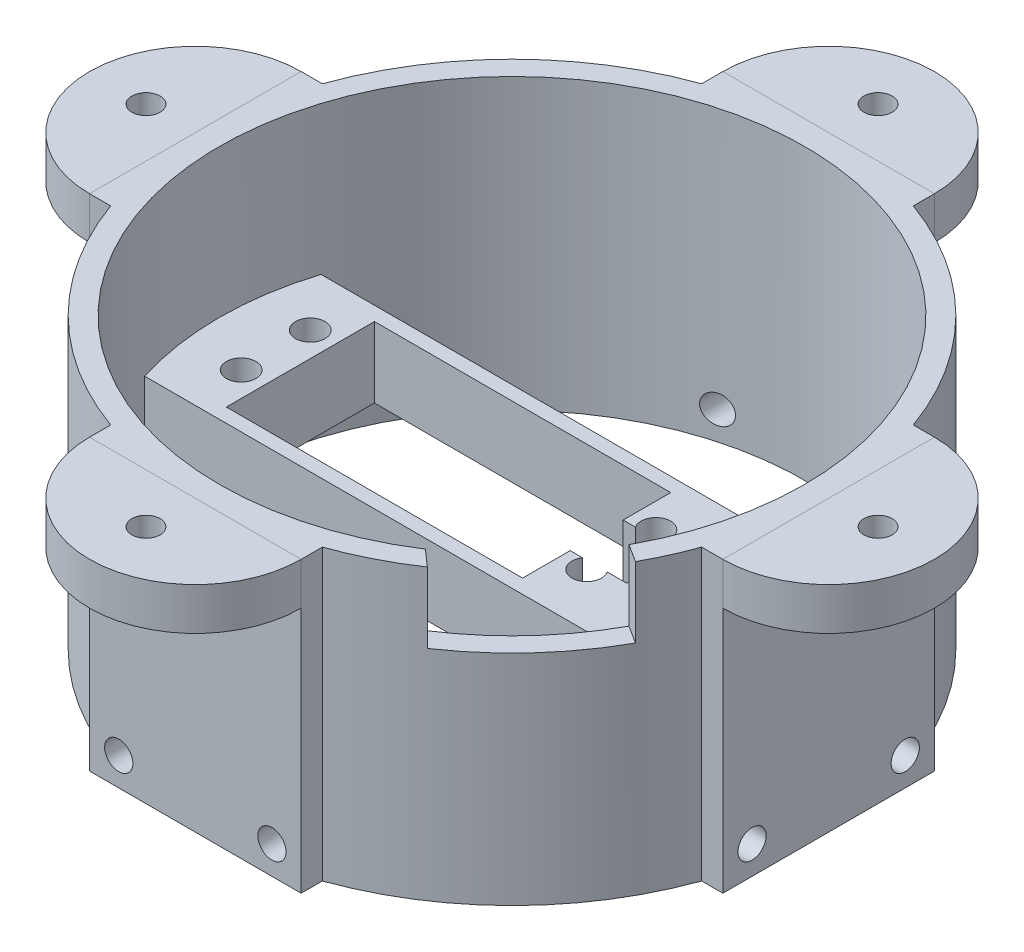
SolidWorks part; units mm, degrees
ref_plane "Front Plane" through (0, 0, 0) normal (0, 0, 1) x (1, 0, 0)
ref_plane "Top Plane" through (0, 0, 0) normal (0, 1, 0) x (1, 0, 0)
ref_plane "Right Plane" through (0, 0, 0) normal (1, 0, 0) x (0, 0, -1)
sketch "Sketch1" plane through (0, 0, 0) normal (0, 1, 0) x (1, 0, 0)
  circle A0 centre (0, 0) radius 44.5
  circle A1 centre (0, 0) radius 41.5
  dimension "D1" = 3
  dimension "D2" = 83
extrude "Boss-Extrude1" add sketch "Sketch1" along normal blind 41
sketch "Sketch2" plane through (0, 0, 0) normal (0, 1, 0) x (1, 0, 0)
  line L0 (-39.5727, 12.5) -> (39.5727, 12.5)
  line L1 (-39.5727, -12.5) -> (39.5727, -12.5)
  line L2 (-9, 10.5) -> (-9, -15.318) construction
  line L3 (-30, 10.5) -> (12, 10.5)
  line L4 (-30, 10.5) -> (-30, -10.5)
  line L5 (-30, -10.5) -> (12, -10.5)
  line L6 (12, 10.5) -> (12, -10.5)
  circle A0 centre (0, 0) radius 41.5 construction
  arc A1 (-39.5727, 12.5) -> (-39.5727, -12.5) centre (-3.1584, 0) ccw
  arc A2 (39.5727, 12.5) -> (39.5727, -12.5) centre (3.1584, 0) cw
  circle A3 centre (15.5, 4.9) radius 2.1
  circle A4 centre (15.5, -4.9) radius 2.1
  circle A7 centre (-33.5, 4.9) radius 2.1
  circle A8 centre (-33.5, -4.9) radius 2.1
  point P6 (0, 0)
  dimension "D5" = 4.2
  dimension "D6" = 4.9
  dimension "D7" = 4.9
  dimension "D11" = 0
  dimension "D1" = 12.5
  dimension "D2" = 12.5
  dimension "D3" = 21
  dimension "D4" = 42
  dimension "D8" = 10.5
  dimension "D9" = 12
  dimension "D10" = 3.5
extrude "Boss-Extrude2" add sketch "Sketch2" along normal blind 20
sketch "Sketch3" plane through (0, 0, 0) normal (0, 1, 0) x (1, 0, 0)
  line L0 (0, 0) -> (0, 56.6556) construction
  line L1 (0, 44.8957) -> (-15, 44.8957)
  line L2 (-15, 44.8957) -> (-15, 41.8957)
  line L3 (0, 44.8957) -> (15, 44.8957)
  line L4 (15, 44.8957) -> (15, 41.8957)
  circle A0 centre (0, 0) radius 44.5 construction
  arc A1 (-15, 41.8957) -> (15, 41.8957) centre (0, 0) cw
  dimension "D1" = 15
  dimension "D2" = 15
  dimension "D3" = 3
extrude "Boss-Extrude3" add sketch "Sketch3" along normal blind 41
pattern_circular "CirPattern1" count 4 over 360 about axis through (0, 41, 0) along (0, -1, 0) of "Boss-Extrude3"
sketch "Sketch4" plane through (-44.8957, 0, 0) normal (-1, 0, 0) x (0, 0, 1)
  line L1 (0, 37.0728) -> (0, -4.8522) construction
  line L2 (-15, 0) -> (15, 0) construction
  line L3 (15, 41) -> (15, 0) construction
  circle A0 centre (10.8598, 4) radius 2
  circle A2 centre (-10.8598, 4) radius 2
  dimension "D1" = 4
  dimension "D2" = 4
  dimension "D3" = 4.1402
extrude "Cut-Extrude1" cut sketch "Sketch4" against normal blind 7
sketch "Sketch5" plane through (0, 0, 0) normal (0, 1, 0) x (1, 0, 0)
  line L0 (-39.5727, 12.5) -> (39.5727, 12.5)
  line L1 (-39.5727, -12.5) -> (39.5727, -12.5)
  arc A0 (-39.5727, 12.5) -> (-39.5727, -12.5) centre (0, 0) ccw
  arc A1 (39.5727, -12.5) -> (39.5727, 12.5) centre (0, 0) ccw
extrude "Cut-Extrude2" cut sketch "Sketch5" along normal blind 10
pattern_circular "CirPattern2" count 4 over 360 about axis through (0, 41, 0) along (0, -1, 0) of "Cut-Extrude1" reverse direction yes
sketch "Sketch6" plane through (0, 41, 0) normal (0, 1, 0) x (1, 0, 0)
  line L0 (-44.8957, 15) -> (-44.8957, -15)
  line L1 (44.8957, -15) -> (44.8957, 15) construction
  line L2 (-15, 44.8957) -> (15, 44.8957)
  line L3 (44.8957, 15) -> (44.8957, -15)
  line L4 (15, -44.8957) -> (-15, -44.8957)
  arc A0 (-44.8957, 15) -> (-44.8957, -15) centre (-44.8957, 0) ccw
  circle A1 centre (-51.8957, 0) radius 2
  arc A2 (44.8957, 15) -> (44.8957, -15) centre (44.8957, 0) cw
  arc A3 (15, -44.8957) -> (-15, -44.8957) centre (0, -44.8957) cw
  arc A4 (-15, 44.8957) -> (15, 44.8957) centre (0, 44.8957) cw
  circle A5 centre (51.8957, 0) radius 2
  circle A6 centre (0, 51.8957) radius 2
  circle A7 centre (0, -51.8957) radius 2
  dimension "D1" = 4
  dimension "D2" = 7
  dimension "D3" = 7
  dimension "D4" = 7
  dimension "D5" = 7
extrude "Boss-Extrude4" add sketch "Sketch6" against normal blind 6 separate body
sketch "Sketch8" plane through (0, 0, 0) normal (0, 1, 0) x (1, 0, 0)
  line L0 (12, 3.75) -> (20, 3.75)
  line L1 (12, -10.5) -> (12, 10.5) construction
  line L2 (20, 3.75) -> (20, -3.75)
  line L3 (20, -3.75) -> (12, -3.75)
  line L4 (12, 3.75) -> (12, -3.75)
  dimension "D1" = 8
  dimension "D2" = 3.75
  dimension "D3" = 3.75
extrude "Cut-Extrude3" cut sketch "Sketch8" along normal blind 60
sketch "Sketch9" plane through (0, 41, 0) normal (0, 1, 0) x (1, 0, 0)
  line L0 (36.4415, -19.8562) -> (38.9762, -21.4734)
  line L1 (24.8878, -36.8897) -> (22.5565, -34.8347)
  arc A0 (36.4415, -19.8562) -> (22.5565, -34.8347) centre (0, 0) cw
  circle A1 centre (0, 0) radius 41.5 construction
  arc A2 (38.9762, -21.4734) -> (24.8878, -36.8897) centre (0, 0) cw
  arc A3 (15, -41.8957) -> (41.8957, -15) centre (0, 0) ccw construction
extrude "Cut-Extrude4" cut sketch "Sketch9" against normal blind 10
